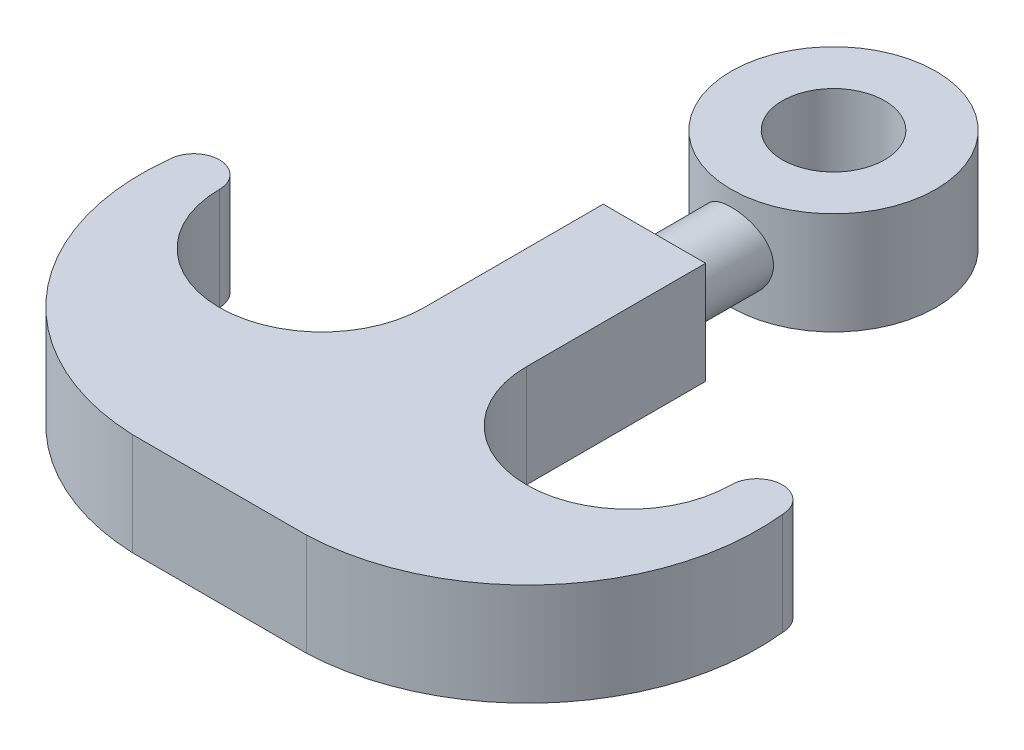
SolidWorks part; units mm, degrees
ref_plane "Front Plane" through (0, 0, 0) normal (0, 0, 1) x (1, 0, 0)
ref_plane "Top Plane" through (0, 0, 0) normal (0, 1, 0) x (1, 0, 0)
ref_plane "Right Plane" through (0, 0, 0) normal (1, 0, 0) x (0, 0, -1)
sketch "Sketch4" plane through (0, 0, 0) normal (0, 1, 0) x (1, 0, 0)
  line L0 (0, 0) -> (0, -70) construction
  line L1 (-43.7747, -70) -> (43.7747, -70) construction
  line L2 (0, -70) -> (0, -120) construction
  line L3 (-10, -35) -> (10, -35)
  line L4 (10, -35) -> (10, -70)
  line L5 (-17, -120) -> (17, -120)
  line L6 (-32.6037, -75) -> (32.6037, -75) construction
  line L7 (-10, -35) -> (-10, -70)
  arc A0 (10, -70) -> (50, -70) centre (30, -70) ccw
  arc A1 (17, -120) -> (60, -70) centre (15.2442, -75) ccw
  arc A2 (50, -70) -> (60, -70) centre (55, -70) cw
  arc A3 (-10, -70) -> (-50, -70) centre (-30, -70) cw
  arc A4 (-50, -70) -> (-60, -70) centre (-55, -70) ccw
  arc A5 (-17, -120) -> (-60, -70) centre (-15.2442, -75) cw
  circle A6 centre (0, 0) radius 20
  circle A7 centre (0, 0) radius 10
  point P17 (0, -35)
  point P19 (0, -75)
  dimension "D5" = 20
  dimension "D8" = 5
  dimension "D9" = 45.0342
  dimension "D10" = 20
  dimension "D11" = 40
  dimension "D1" = 70
  dimension "D2" = 50
  dimension "D3" = 10
  dimension "D4" = 35
  dimension "D6" = 17
  dimension "D7" = 45
sketch "Sketch5" plane through (0, 0, 0) normal (0, 1, 0) x (1, 0, 0)
  line L0 (-10, -35) -> (10, -35)
  line L1 (-7, -32) -> (-7, -18.735)
  line L2 (0, 0) -> (0, -70) construction
  line L3 (0, -35) -> (0, -54.6835) construction
  arc A0 (-10, -35) -> (-7, -32) centre (-10, -32) ccw
  circle A1 centre (0, 0) radius 20 construction
  point P6 (-7, -25.3675)
  dimension "D2" = 3
  dimension "D1" = 7
extrude "Boss-Extrude1" add sketch "Sketch4" along normal blind 10 and the other way blind 10
sketch "Sketch6" plane through (0, 0, 35) normal (0, 0, -1) x (-1, 0, 0)
  circle A0 centre (0, 0) radius 7
  dimension "D1" = 14
extrude "Boss-Extrude2" add sketch "Sketch6" along normal blind 20
fillet "Fillet1" radius 3 1 edges at (-7, 0, 35)
equation "\"¨34\"=30"
